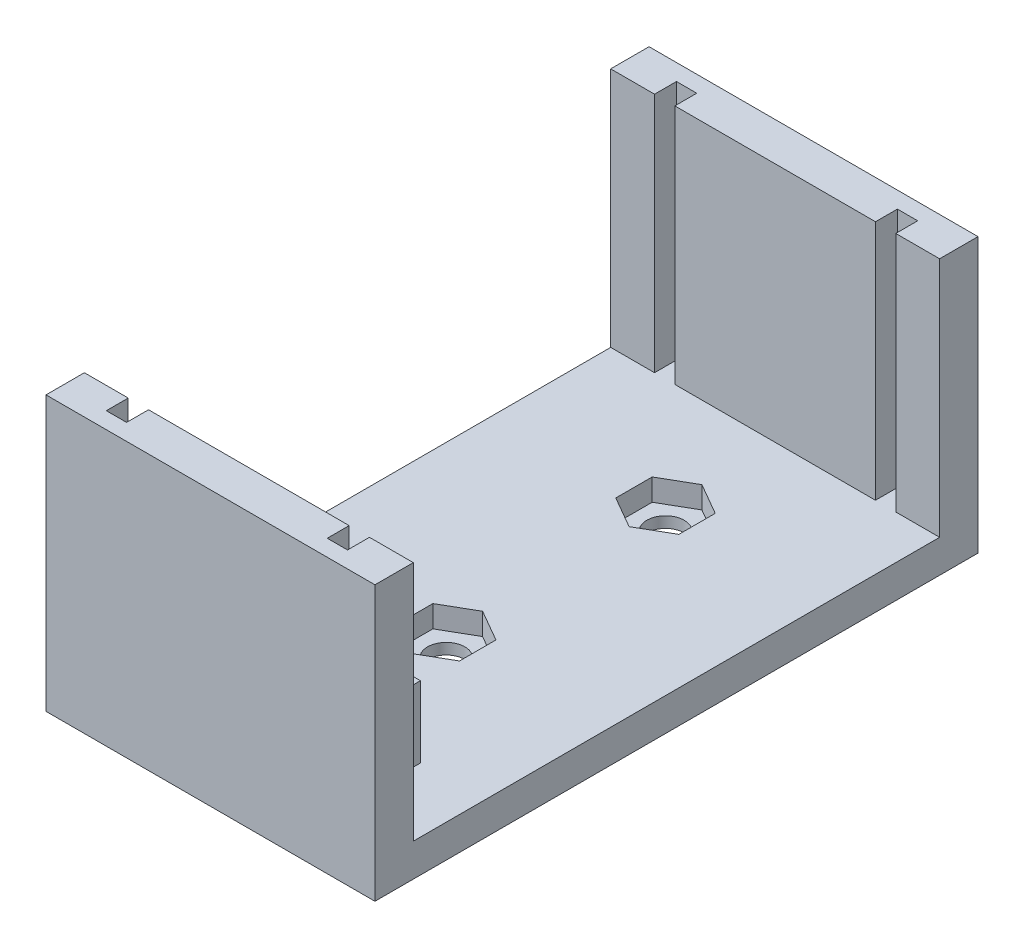
SolidWorks part; units mm, degrees
ref_plane "Front Plane" through (0, 0, 0) normal (0, 0, 1) x (1, 0, 0)
ref_plane "Top Plane" through (0, 0, 0) normal (0, 1, 0) x (1, 0, 0)
ref_plane "Right Plane" through (0, 0, 0) normal (1, 0, 0) x (0, 0, -1)
sketch "Sketch1" plane through (0, 0, 0) normal (0, 1, 0) x (1, 0, 0)
  line L0 (0, 27.5) -> (0, -27.5) construction
  line L1 (-15, 27.5) -> (15, 27.5)
  line L2 (-15, 27.5) -> (-15, -27.5)
  line L3 (-15, -27.5) -> (15, -27.5)
  line L4 (15, 27.5) -> (15, -27.5)
  line L5 (-15, 27.5) -> (15, -27.5) construction
  line L6 (-15, -27.5) -> (15, 27.5) construction
  line L7 (15, 0) -> (-15, 0) construction
  line L8 (-15, 24) -> (-11, 24)
  line L9 (-11, 24) -> (-11, 26)
  line L10 (-11, 26) -> (-9.15, 26)
  line L11 (-9.15, 26) -> (-9.15, 24)
  line L12 (-9.15, 24) -> (9.15, 24)
  line L13 (11, 24) -> (11, 26)
  line L14 (9.15, 26) -> (9.15, 24)
  line L15 (11, 26) -> (9.15, 26)
  line L16 (-15, 27.5) -> (-15, -27.5)
  line L17 (15, 27.5) -> (15, -27.5)
  line L18 (15, 24) -> (11, 24)
  line L19 (-15, -24) -> (-11, -24)
  line L20 (-11, -24) -> (-11, -26)
  line L21 (-11, -26) -> (-9.15, -26)
  line L22 (-9.15, -26) -> (-9.15, -24)
  line L23 (15, -24) -> (11, -24)
  line L24 (11, -24) -> (11, -26)
  line L25 (11, -26) -> (9.15, -26)
  line L26 (-9.15, -24) -> (9.15, -24)
  line L27 (9.15, -26) -> (9.15, -24)
  point P0 (0, 0)
  point P20 (0, 24)
  dimension "D1" = 30
  dimension "D2" = 55
  dimension "D3" = 26
  dimension "D4" = 2
  dimension "D5" = 2
  dimension "D6" = 1.85
  dimension "D7" = 4
extrude "Boss-Extrude1" add sketch "Sketch1" along normal blind 25 contours L25 L27 L26 L22 L21 L20 L19 L16 L3 L4 L23 L24 | L18 L4 L1 L2 L8 L9 L10 L11 L12 L14 L15 L13 region at (0, 0, -25.8069) region at (0, 0, 25.8069)
extrude "Boss-Extrude2" add sketch "Sketch1<3>" along normal blind 3 contours L27 L25 L24 L23 L17 L18 L13 L15 L14 L12 L11 L10 L9 L8 L2 L19 L20 L21 L22 L26 region at (0, 0, 0)
sketch "Sketch1<3>" plane through (0, 0, 0) normal (0, 1, 0) x (1, 0, 0) same geometry as "Sketch1"
sketch "Sketch2" plane through (0, 3, 0) normal (0, 1, 0) x (1, 0, 0)
  line L0 (0, 24) -> (0, -24) construction
  line L1 (9.15, -26) -> (9.15, -24) construction
  line L3 (-9.15, 24) -> (9.15, 24) construction
  line L4 (-9.15, -24) -> (9.15, -24) construction
  line L6 (-9.15, -24) -> (9.15, -24)
  line L7 (-9.15, -24) -> (-9.15, -17.5)
  line L8 (-9.15, -17.5) -> (9.15, -17.5)
  line L9 (9.15, -24) -> (9.15, -17.5)
  dimension "D1" = 6.5
extrude "Boss-Extrude3" add sketch "Sketch2" along normal blind 6.5
sketch "Sketch3" plane through (9.15, 0, 0) normal (1, 0, 0) x (0, 0, -1)
  line L0 (-17.5, 9.5) -> (-24, 9.5) construction
  line L1 (-24, 9.5) -> (-24, 3) construction
  line L2 (-24, 3) -> (-17.5, 3) construction
  line L3 (-17.5, 9.5) -> (-17.5, 3) construction
  circle A0 centre (-20.75, 6.25) radius 1.6
  dimension "D3" = 3.2
  dimension "D1" = 3.25
  dimension "D2" = 3.25
extrude "Cut-Extrude1" cut sketch "Sketch3" against normal up to next
sketch "Sketch4" plane through (0, 3, 0) normal (0, 1, 0) x (1, 0, 0)
  line L0 (0, -17.5) -> (0, 24) construction
  line L1 (9.15, -17.5) -> (-9.15, -17.5) construction
  line L2 (-9.15, 24) -> (9.15, 24) construction
  line L4 (-2.875, 12.3401) -> (0, 10.6802)
  line L5 (0, 10.6802) -> (2.875, 12.3401)
  line L6 (2.875, 12.3401) -> (2.875, 15.6599)
  line L7 (2.875, 15.6599) -> (0, 17.3198)
  line L8 (0, 17.3198) -> (-2.875, 15.6599)
  line L9 (-2.875, 15.6599) -> (-2.875, 12.3401)
  line L10 (0, -9.3198) -> (2.875, -7.6599)
  line L11 (2.875, -7.6599) -> (2.875, -4.3401)
  line L12 (2.875, -4.3401) -> (0, -2.6802)
  line L13 (0, -2.6802) -> (-2.875, -4.3401)
  line L14 (-2.875, -4.3401) -> (-2.875, -7.6599)
  line L15 (-2.875, -7.6599) -> (0, -9.3198)
  circle A0 centre (0, 14) radius 2.875 construction
  circle A1 centre (0, -6) radius 2.875 construction
  circle A2 centre (0, 14) radius 1.7
  circle A3 centre (0, -6) radius 1.7
  dimension "D3" = 5.75
  dimension "D4" = 5.75
  dimension "D5" = 3.4
  dimension "D6" = 3.4
  dimension "D1" = 10
  dimension "D2" = 20
extrude "Cut-Extrude2" cut sketch "Sketch4" against normal up to next contours A3 | A2 region at (0, 3, 6)
extrude "Cut-Extrude3" cut sketch "Sketch4<3>" against normal blind 2
sketch "Sketch4<3>" plane through (0, 3, 0) normal (0, 1, 0) x (1, 0, 0) same geometry as "Sketch4"
